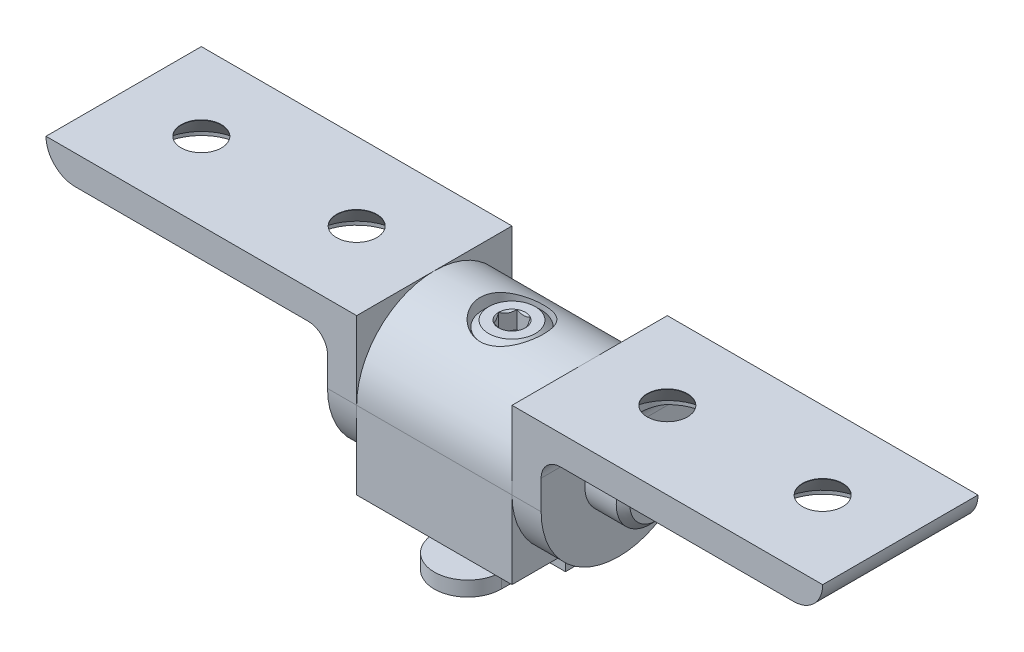
SolidWorks part; units mm, degrees
ref_plane "Front Plane" through (0, 0, 0) normal (0, 0, 1) x (1, 0, 0)
ref_plane "Top Plane" through (0, 0, 0) normal (0, 1, 0) x (1, 0, 0)
ref_plane "Right Plane" through (0, 0, 0) normal (1, 0, 0) x (0, 0, -1)
sketch "Sketch1" plane through (0, 0, 0) normal (1, 0, 0) x (0, 0, -1)
  line L0 (0, 0) -> (0, -6.985) construction
  line L2 (-12.7, 12.7) -> (-12.7, 0) construction
  line L3 (-12.7, 0) -> (12.7, 0) construction
  line L4 (12.7, 12.7) -> (12.7, 0) construction
  line L5 (-4.7625, 24.765) -> (4.7625, 24.765) construction
  line L7 (12.7, 0) -> (12.7, -2.54) construction
  line L12 (12.7, -2.54) -> (4.7752, -2.54) construction
  line L13 (-5.1911, 18.415) -> (5.1911, 18.415) construction
  line L14 (-3.2982, 12.7) -> (3.2982, 12.7) construction
  line L15 (0, 18.415) -> (0, 24.765) construction
  line L16 (-3.175, 19.5263) -> (-3.175, 18.415) construction
  line L17 (-3.175, 18.415) -> (-2.3501, 18.8913) construction
  line L18 (-2.3501, 18.8913) -> (-2.3501, 19.05) construction
  line L19 (-2.3501, 19.05) -> (-3.175, 19.5263) construction
  line L20 (-2.3501, 18.9706) -> (-3.175, 18.9706) construction
  line L21 (-3.175, 19.5263) -> (-3.3125, 19.6056) construction
  line L22 (-3.3125, 19.6056) -> (-3.3125, 18.3356) construction
  line L23 (-3.3125, 18.3356) -> (-3.175, 18.415) construction
  line L24 (-2.7626, 19.2881) -> (-2.7626, 18.6531) construction
  line L25 (-3.175, 18.9706) -> (-3.3125, 18.9706) construction
  circle A1 centre (0, 12.7) radius 3.175 construction
  circle A2 centre (0, 12.7) radius 12.7 construction
  point P6 (0, 25.4)
  point P11 (0, 18.415)
  point P20 (0, -6.985)
  point P24 (0, 18.415)
  point P25 (0, 12.7)
  point P45 (3.175, 12.7)
  dimension "D3" = 60
  dimension "D4" = 0.635
  dimension "D5" = 0.1588
sketch "Sketch6" plane through (0, 0, 0) normal (0, 0, 1) x (1, 0, 0)
  line L1 (12.7, 0) -> (-12.7, 0) construction
  line L5 (-23.7109, 18.2563) -> (-17.4625, 18.2563) construction
  line L6 (-12.7, 0) -> (-63.5, 0) construction
  line L7 (-17.4625, 18.2563) -> (-17.4625, 17.4625) construction
  line L10 (-17.4625, 17.4625) -> (-12.7, 17.4625) construction
  line L11 (-12.7, 17.4625) -> (-12.7, 15.875) construction
  line L12 (-12.7, 15.875) -> (-6.35, 15.875) construction
  line L13 (-6.35, 15.875) -> (-6.35, 9.525) construction
  line L14 (-6.35, 9.525) -> (-12.7, 9.525) construction
  line L15 (-12.7, 9.525) -> (-12.7, 7.9375) construction
  line L16 (-12.7, 7.9375) -> (-17.4625, 7.9375) construction
  line L19 (-17.4625, 7.9375) -> (-17.4625, 7.1438) construction
  line L20 (-17.4625, 7.1438) -> (-23.7109, 7.1438) construction
  line L21 (-23.7109, 7.1438) -> (-23.7109, 18.2563) construction
  line L22 (-23.7109, 12.7) -> (-6.35, 12.7) construction
  line L23 (12.7, 0) -> (63.5, 0) construction
  line L24 (-63.5, 0) -> (-63.5, 4.7625) construction
  line L25 (63.5, 0) -> (63.5, 4.7625) construction
  point P12 (0, 0)
  point P18 (-25.4, 0)
  point P23 (-50.8, 0)
  point P25 (-38.1, 0)
  dimension "D6" = 6.35
  dimension "D1" = 12.7
sketch "Sketch2" plane through (0, 0, 0) normal (1, 0, 0) x (0, 0, -1)
  line L0 (12.7, 12.7) -> (12.7, 0) construction
  line L1 (-12.7, 0) -> (12.7, 0) construction
  line L2 (-12.7, 12.7) -> (-12.7, 0) construction
  line L3 (12.7, 12.7) -> (12.7, 0)
  line L4 (-12.7, 0) -> (12.7, 0)
  line L5 (-12.7, 12.7) -> (-12.7, 0)
  circle A0 centre (0, 12.7) radius 3.175 construction
  circle A2 centre (0, 12.7) radius 3.175
  arc A4 (-12.7, 12.7) -> (12.7, 12.7) centre (0, 12.7) cw
extrude "Boss-Extrude1" add sketch "Sketch2" along normal mid plane 25.4 contours A4 L5 L4 L3 A2
sketch "Sketch3" plane through (0, 0, 0) normal (1, 0, 0) x (0, 0, -1)
  line L11 (4.7752, -2.54) -> (12.7, -2.54)
  line L12 (4.7752, -2.54) -> (4.7752, 0)
  line L13 (4.7752, 0) -> (12.7, 0)
  line L14 (12.7, -2.54) -> (12.7, 0)
  line L15 (-12.7, 0) -> (-4.7752, 0)
  line L16 (-12.7, 0) -> (-12.7, -2.54)
  line L17 (-12.7, -2.54) -> (-4.7752, -2.54)
  line L18 (-4.7752, 0) -> (-4.7752, -2.54)
  dimension "D1" = 2.54
  dimension "D2" = 7.9248
extrude "Boss-Extrude2" [suppressed] add sketch "Sketch3" along normal mid plane 7.9248
sketch "Sketch4" plane through (0, 0, 0) normal (0, 0, 1) x (1, 0, 0)
  line L0 (12.7, 12.7) -> (12.7, 0) construction
  line L9 (12.7, 0) -> (-12.7, 0) construction
  line L11 (4.7752, -2.54) -> (12.7, -2.54)
  line L12 (4.7752, -2.54) -> (4.7752, 0)
  line L13 (4.7752, 0) -> (12.7, 0)
  line L14 (12.7, -2.54) -> (12.7, 0)
  line L15 (-12.7, 0) -> (-4.7752, 0)
  line L16 (-12.7, 0) -> (-12.7, -2.54)
  line L17 (-12.7, -2.54) -> (-4.7752, -2.54)
  line L18 (-4.7752, 0) -> (-4.7752, -2.54)
  dimension "D1" = 7.9248
  dimension "D2" = 2.54
extrude "Boss-Extrude3" add sketch "Sketch4" along normal mid plane 7.9248
sketch "Sketch22" plane through (0, 0, 0) normal (0, 0, 1) x (1, 0, 0)
  line L6 (-12.7, 0) -> (-12.7, 25.4)
  line L7 (-12.7, 25.4) -> (-63.5, 25.4)
  line L9 (-58.7375, 20.6375) -> (-20.6375, 20.6375)
  line L10 (-17.4625, 17.4625) -> (-17.4625, 0)
  line L11 (-12.7, 0) -> (-63.5, 0) construction
  line L12 (-17.4625, 0) -> (-12.7, 0)
  line L13 (-20.6375, 20.6375) -> (-20.6375, 25.4) construction
  line L14 (-17.4625, 17.4625) -> (-12.7, 17.4625) construction
  line L15 (-63.5, 0) -> (-63.5, 4.7625) construction
  arc A2 (-17.4625, 17.4625) -> (-20.6375, 20.6375) centre (-20.6375, 17.4625) ccw
  arc A3 (-58.7375, 20.6375) -> (-63.5, 25.4) centre (-58.7375, 25.4) cw
  dimension "D1" = 3.175
extrude "Boss-Extrude8" add sketch "Sketch22" along normal mid plane 25.4 separate body
sketch "Sketch23" plane through (-17.4625, 0, 0) normal (-1, 0, 0) x (0, 0, 1)
  line L3 (12.7, 12.7) -> (12.7, 0) construction
  line L4 (-12.7, 12.7) -> (-12.7, -6.985)
  line L5 (-12.7, -6.985) -> (12.7, -6.985)
  line L6 (12.7, -6.985) -> (12.7, 12.7)
  circle A1 centre (0, 12.7) radius 4.7625
  arc A2 (-12.7, 12.7) -> (12.7, 12.7) centre (0, 12.7) ccw
  circle A3 centre (0, 12.7) radius 12.7 construction
extrude "Cut-Extrude7" cut sketch "Sketch23" against normal through all
sketch "Sketch24" plane through (0, 0, 0) normal (0, 0, 1) x (1, 0, 0)
  line L0 (-50.8, 0) -> (-50.8, 25.4) construction
  line L11 (-12.7, 25.4) -> (-63.5, 25.4) construction
  line L12 (-54.0982, 25.4) -> (-54.0982, 25.3319)
  line L13 (-54.0982, 25.3319) -> (-57.6821, 21.209)
  line L14 (-57.6821, 21.209) -> (-57.6821, 20.6375)
  line L15 (-58.7375, 20.6375) -> (-20.6375, 20.6375) construction
  line L16 (-57.6821, 20.6375) -> (-50.8, 20.6375) construction
  line L17 (-50.8, 20.6375) -> (-50.8, 25.4)
  line L18 (-50.8, 25.4) -> (-54.0982, 25.4)
  line L19 (-57.6821, 20.6375) -> (-57.6821, 12.7)
  line L20 (-57.6821, 12.7) -> (-50.8, 12.7)
  line L21 (-50.8, 12.7) -> (-50.8, 20.6375)
  line L22 (-23.7109, 12.7) -> (-6.35, 12.7) construction
  dimension "D1" = 49
  dimension "D2" = 6.5964
  dimension "D3" = 13.7643
  dimension "D4" = 0.5715
revolve "Cut-Revolve1" cut sketch "Sketch24" angle 360 about L0
pattern_linear "LPattern1" count 2 spacing 25.4 along (1, 0, 0) of "Cut-Revolve1"
sketch "Sketch8" plane through (0, 0, 0) normal (0, 0, 1) x (1, 0, 0)
  line L6 (-22.5997, 18.2563) -> (-17.4625, 18.2563)
  line L9 (-17.4625, 18.2563) -> (-17.4625, 17.4625)
  line L10 (-17.4625, 17.4625) -> (-12.7, 17.4625)
  line L11 (-12.7, 17.4625) -> (-12.7, 15.875)
  line L12 (-12.7, 15.875) -> (-6.35, 15.875)
  line L13 (-6.35, 15.875) -> (-6.35, 12.7)
  line L19 (-23.7109, 12.7) -> (-23.7109, 17.145)
  line L20 (-23.7109, 12.7) -> (-6.35, 12.7)
  line L21 (-23.7109, 12.7) -> (0, 12.7) construction
  line L22 (-23.7109, 17.145) -> (-22.5997, 18.2563)
  dimension "D1" = 45
  dimension "D2" = 1.1113
revolve "Revolve1" add sketch "Sketch8" angle 360 about L21
sketch "Sketch9" plane through (-23.7109, 0, 0) normal (-1, 0, 0) x (0, 0, 1)
  line L1 (0, 14.8997) -> (-1.905, 13.7999)
  line L2 (-1.905, 13.7999) -> (-1.905, 11.6001)
  line L3 (-1.905, 11.6001) -> (0, 10.5003)
  line L4 (0, 10.5003) -> (1.905, 11.6001)
  line L5 (1.905, 11.6001) -> (1.905, 13.7999)
  line L6 (1.905, 13.7999) -> (0, 14.8997)
  circle A0 centre (0, 12.7) radius 1.905 construction
extrude "Cut-Extrude1" cut sketch "Sketch9" against normal blind 2.8575
sketch "Sketch10" plane through (-23.7109, 0, 0) normal (-1, 0, 0) x (0, 0, 1)
  circle A0 centre (0, 12.7) radius 2.1997
extrude "Cut-Extrude2" cut sketch "Sketch10" against normal through all draft 45
mirror "Mirror2" about plane through (0, 0, 0) normal (1, 0, 0) of bodies 111 129 107 126
ref_plane "Plane2" through (0, 18.415, 0) normal (0, 1, 0) x (1, 0, 0)
sketch "Sketch12" plane through (0, 18.415, 0) normal (0, 1, 0) x (1, 0, 0)
  circle A0 centre (0, 0) radius 5.1911
extrude "Cut-Extrude3" cut sketch "Sketch12" along normal through all
sketch "Sketch13" plane through (0, 18.415, 0) normal (0, 1, 0) x (1, 0, 0)
  circle A0 centre (0, 0) radius 3.2982
extrude "Cut-Extrude4" cut sketch "Sketch13" against normal through all
ref_plane "Plane3" through (0, -6.985, 0) normal (0, 1, 0) x (1, 0, 0)
sketch "Sketch14" plane through (0, -6.985, 0) normal (0, 1, 0) x (1, 0, 0)
  line L0 (0, 7.2231) -> (0, -7.2231) construction
  line L1 (5.4769, 7.2231) -> (5.4769, -7.2231)
  line L2 (-5.4769, 7.2231) -> (-5.4769, -7.2231)
  arc A0 (5.4769, 7.2231) -> (-5.4769, 7.2231) centre (0, 7.2231) ccw
  arc A1 (-5.4769, -7.2231) -> (5.4769, -7.2231) centre (0, -7.2231) ccw
  circle A3 centre (0, 0) radius 3.175
  point P2 (0, 0)
  point P10 (0, -12.7)
  dimension "D1" = 6.35
  dimension "D2" = 2.3019
extrude "Boss-Extrude6" add sketch "Sketch14" along normal blind 2.413 separate body
sketch "Sketch16" plane through (0, 18.415, 0) normal (0, 1, 0) x (1, 0, 0)
  circle A0 centre (0, 0) radius 3.175
extrude "Boss-Extrude7" add sketch "Sketch16" against normal up to vertex (25.4 mm away) separate body up to point (0, -6.985, 0)
sketch "Sketch17" plane through (0, 18.415, 0) normal (0, 1, 0) x (1, 0, 0)
  circle A1 centre (0, 0) radius 3.175
  circle A2 centre (0, 0) radius 3.175
  dimension "D1" = 0
sketch "Sketch19" plane through (0, 0, 0) normal (1, 0, 0) x (0, 0, -1)
  line L0 (0, 18.415) -> (0, 24.765)
  line L1 (0, 18.415) -> (0, 24.765) construction
  line L2 (0, 24.765) -> (3.81, 24.765)
  line L3 (3.81, 24.765) -> (4.7625, 23.8125)
  line L4 (4.7625, 23.8125) -> (4.7625, 18.415)
  line L5 (-5.1911, 18.415) -> (5.1911, 18.415) construction
  line L6 (4.7625, 18.415) -> (0, 18.415)
  line L7 (0, 25.4) -> (0, 0) construction
  dimension "D1" = 45
  dimension "D2" = 0.9525
  dimension "D3" = 6.35
revolve "Revolve3" add sketch "Sketch19" angle 360 about L7
sketch "Sketch20" plane through (0, 24.765, 0) normal (0, 1, 0) x (1, 0, 0)
  line L1 (1.0999, 1.905) -> (-1.0999, 1.905)
  line L2 (-1.0999, 1.905) -> (-2.1997, 0)
  line L3 (-2.1997, 0) -> (-1.0999, -1.905)
  line L4 (-1.0999, -1.905) -> (1.0999, -1.905)
  line L5 (1.0999, -1.905) -> (2.1997, 0)
  line L6 (2.1997, 0) -> (1.0999, 1.905)
  circle A0 centre (0, 0) radius 1.905 construction
  dimension "D1" = 3.81
extrude "Cut-Extrude5" cut sketch "Sketch20" against normal blind 2.8575
sketch "Sketch21" plane through (0, 24.765, 0) normal (0, 1, 0) x (1, 0, 0)
  circle A0 centre (0, 0) radius 2.1997
extrude "Cut-Extrude6" cut sketch "Sketch21" against normal through all draft 45
curve "Helix/Spiral1" pitch 1.27 height 26.67 turns 21
sketch "Sketch18" plane through (0, 0, 0) normal (1, 0, 0) x (0, 0, -1)
  line L0 (-3.175, 19.5263) -> (-3.175, 18.415)
  line L1 (-3.175, 18.415) -> (-2.3501, 18.8913)
  line L2 (-2.3501, 18.8913) -> (-2.3501, 19.05)
  line L3 (-2.3501, 19.05) -> (-3.175, 19.5263)
sweep "Cut-Sweep1" cut profiles "Sketch18" path "Helix/Spiral1"
equation "\"D1@Boss-Extrude1\"=\"D@Sketch1\""
equation "\"D1@Boss-Extrude2\"=\"Tab Width@Sketch1\""
equation "\"D2@Sketch4\" = \"Tab Height@Sketch1\""
equation "\"D1@Sketch4\"=\"Tab Width@Sketch1\""
equation "\"D1@Boss-Extrude3\"=\"Tab Width@Sketch1\""
equation "\"D1@Sketch3\"=\"Tab Height@Sketch1\""
equation "\"D2@Sketch3\"=\"Tab Width@Sketch1\""
equation "\"D1@Cut-Extrude1\"=\"Hex Size@Sketch9\"*.75"
equation "\"Screw Clearence@Sketch1\"=\"Thread OD@Sketch1\"*1.0388"
equation "\"D1@Sketch14\"=\"Thread OD@Sketch1\""
equation "\"D4@Sketch1\"=\"Pitch@Sketch1\"/2"
equation "\"D5@Sketch1\"=\"Pitch@Sketch1\"/8"
equation "\"D4@Helix/Spiral1\"=\"Pitch@Sketch1\""
equation "\"D3@Helix/Spiral1\"=\"Thread Length@Sketch1\"+\"Pitch@Sketch1\""
equation "\"D2@Sketch19\"=\"Head Dia@Sketch1\"*.1"
equation "\"D3@Sketch19\"=\"Head Height@Sketch1\""
equation "\"D1@Sketch20\"=\"Hex Size@Sketch9\""
equation "\"D1@Cut-Extrude5\"=\"D1@Cut-Extrude1\""
equation "\"D2@Sketch8\" = \"Shoulder Head Dia@Sketch6\" * .1"
equation "\"Head Height@Sketch1\"=\"Thread OD@Sketch1\""
equation "\"D6@Sketch6\"=\"Thread OD@Sketch1\""
equation "\"Head Dia@Sketch1\"=\"Thread OD@Sketch1\"*1.5"
equation "\"Shoulder Head Dia@Sketch6\"=1.75*\"Thread OD@Sketch1\""
equation "\"C'Bore Dia@Sketch1\"=1.09*\"Head Dia@Sketch1\""
equation "\"Hex Size@Sketch9\"=\"Thread OD@Sketch1\"*.6"
equation "\"D1@Sketch6\" = .5 * \"C@Sketch6\""
equation "\"Pivot Width@Sketch6\"=\"D@Sketch1\""
equation "\"D1@Boss-Extrude8\"=\"D@Sketch1\""
equation "\"D3@LPattern1\"=\"C@Sketch6\""
equation "\"D2@Sketch24\"=\"Thread OD@Sketch1\"*1.0388"
equation "\"D3@Sketch24\"=\"Thread OD@Sketch1\"*2.1676"
equation "\"D4@Sketch24\"=.09*\"Thread OD@Sketch1\""
